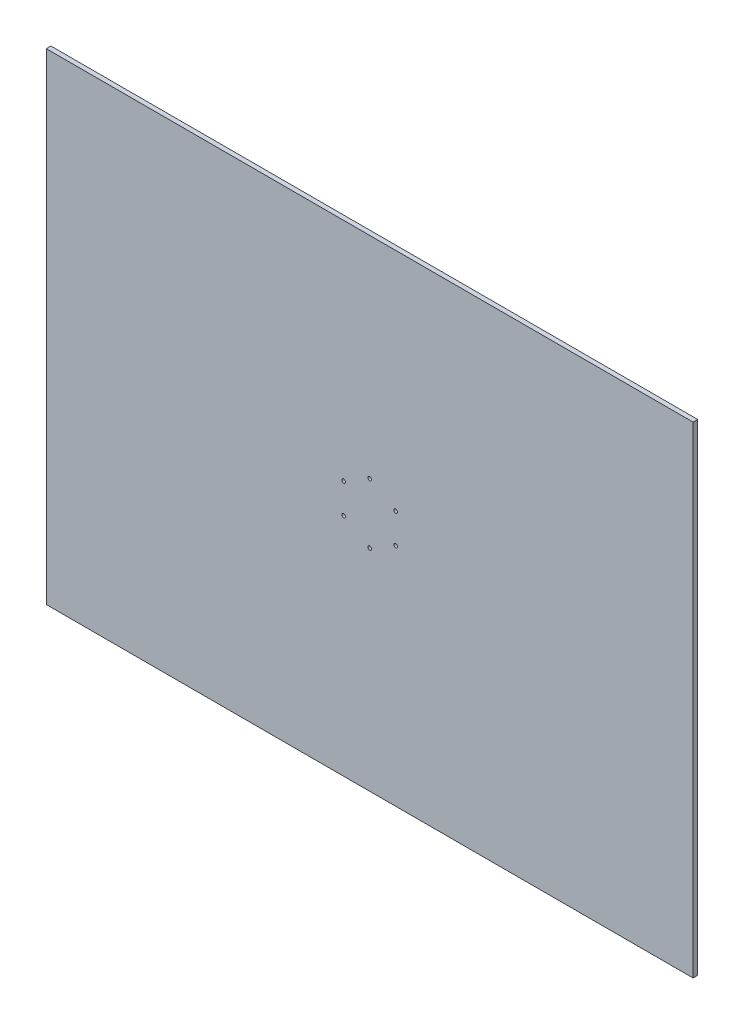
SolidWorks part; units mm, degrees
ref_plane "Front Plane" through (0, 0, 0) normal (0, 0, 1) x (1, 0, 0)
ref_plane "Top Plane" through (0, 0, 0) normal (0, 1, 0) x (1, 0, 0)
ref_plane "Right Plane" through (0, 0, 0) normal (1, 0, 0) x (0, 0, -1)
sketch "Sketch1" plane through (0, 0, 0) normal (0, 0, 1) x (1, 0, 0)
  line L0 (0, 310.6806) -> (0, -302.44) construction
  line L1 (-300, -260.5) -> (400, -260.5)
  line L2 (-300, -260.5) -> (-300, 260.5)
  line L3 (-300, 260.5) -> (400, 260.5)
  line L4 (400, -260.5) -> (400, 260.5)
  line L5 (-603.6567, 0) -> (628.0589, 0) construction
  line L6 (0, -310.6806) -> (0, 302.44) construction
  line L7 (-300, -260.5) -> (400, -260.5)
  line L8 (-300, 260.5) -> (400, 260.5)
  point P0 (0, 0)
  point P6 (0, 0)
  dimension "D1" = 700
  dimension "D2" = 521
  dimension "D11" = 300
extrude "Boss-Extrude1" add sketch "Sketch1" along normal blind 5 contours L1 L4 L3 L2 region at (50, 0, 0)
sketch "Sketch2" plane through (0, 0, 5) normal (0, 0, 1) x (1, 0, 0)
  line L0 (50, 30.5) -> (50, -260.5) construction
  line L1 (50, 260.5) -> (50, 34.5) construction
  line L2 (-300, 260.5) -> (400, 260.5) construction
  line L3 (-300, -260.5) -> (400, -260.5) construction
  circle A8 centre (50, 32.5) radius 2
  circle A9 centre (78.1458, 16.25) radius 2
  circle A10 centre (78.1458, -16.25) radius 2
  circle A11 centre (50, -32.5) radius 2
  circle A12 centre (21.8542, -16.25) radius 2
  circle A13 centre (21.8542, 16.25) radius 2
  point P24 (50, 0)
  dimension "D2" = 4
extrude "Cut-Extrude1" cut sketch "Sketch2" against normal blind 10
